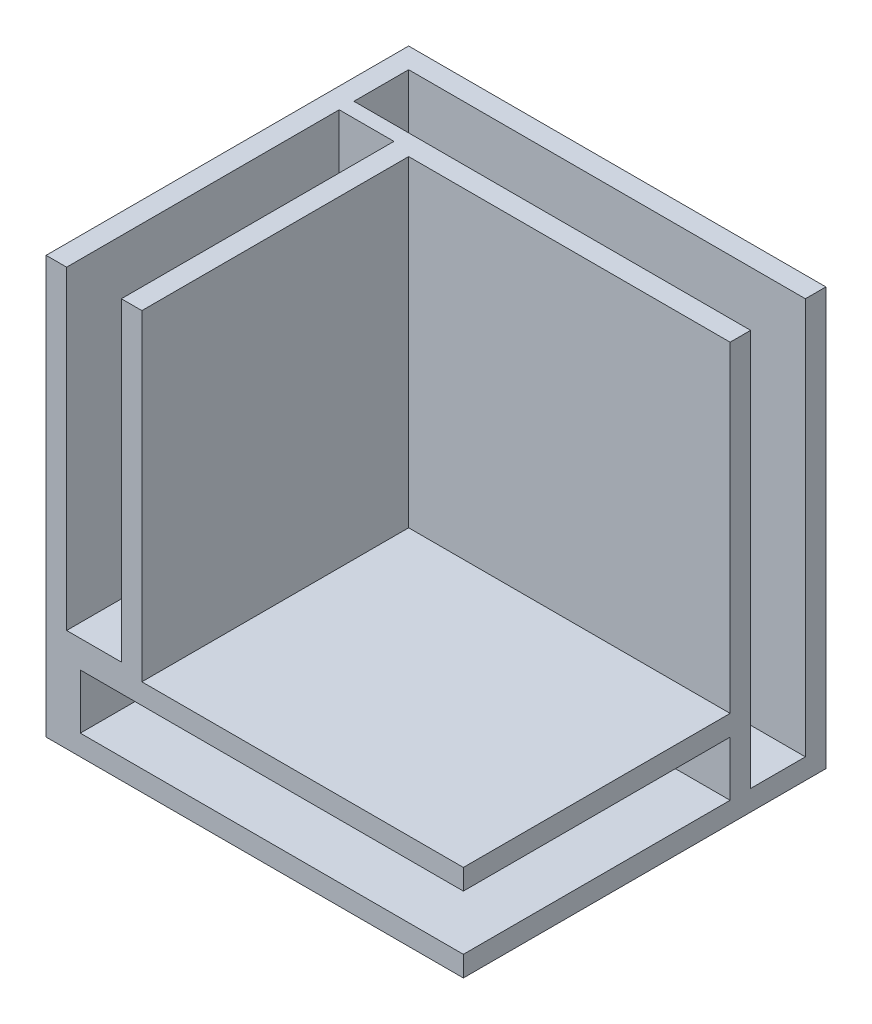
SolidWorks part; units mm, degrees
ref_plane "Front Plane" through (0, 0, 0) normal (0, 0, 1) x (1, 0, 0)
ref_plane "Top Plane" through (0, 0, 0) normal (0, 1, 0) x (1, 0, 0)
ref_plane "Right Plane" through (0, 0, 0) normal (1, 0, 0) x (0, 0, -1)
sketch "Sketch1" plane through (0, 0, 0) normal (0, 0, 1) x (1, 0, 0)
  line L1 (0, 0) -> (30, 0)
  line L2 (0, 0) -> (0, 30)
  line L3 (0, 30) -> (30, 30)
  line L4 (30, 0) -> (30, 30)
  dimension "D1" = 30
  dimension "D2" = 30
extrude "Boss-Extrude1" add sketch "Sketch1" along normal blind 6
sketch "Sketch2" plane through (0, 0, 6) normal (0, 0, 1) x (1, 0, 0)
  line L0 (0, 0) -> (30, 0) construction
  line L5 (6, 6) -> (0, 6)
  line L6 (30, 0) -> (6, 0)
  line L7 (30, 0) -> (30, 6)
  line L8 (30, 6) -> (6, 6)
  line L9 (6, 0) -> (6, 6)
  line L10 (6, 6) -> (6, 30)
  line L11 (30, 30) -> (0, 30) construction
  line L12 (6, 30) -> (0, 30)
  line L13 (0, 30) -> (0, 6)
  line L15 (5, 6) -> (6, 6)
  line L16 (5, 6) -> (5, 5)
  line L17 (5, 5) -> (6, 5)
  line L18 (6, 6) -> (6, 5)
  line M7 (0, 30) -> (0, 0)
  line M10 (30, 30) -> (0, 30)
  dimension "D1" = 6
  dimension "D2" = 6
  dimension "D3" = 1
  dimension "D4" = 1
extrude "Boss-Extrude4" add sketch "Sketch2" along normal blind 20 contours L5 L10 M10 M7 region at (3, 18, 6)
sketch "Sketch3" plane through (0, 0, 6) normal (0, 0, 1) x (1, 0, 0)
  line L1 (30, 0) -> (6, 0)
  line L2 (30, 0) -> (30, 6)
  line L3 (30, 6) -> (6, 6)
  line L4 (6, 0) -> (6, 6)
sketch "Sketch4" plane through (0, 0, 6) normal (0, 0, 1) x (1, 0, 0)
  line L1 (6, 6) -> (4, 6)
  line L2 (6, 6) -> (6, 4)
  line L3 (6, 4) -> (4, 4)
  line L4 (4, 6) -> (4, 4)
  dimension "D1" = 2
  dimension "D2" = 2
extrude "Boss-Extrude6" add sketch "Sketch4" along normal blind 20
sketch "Sketch5" plane through (0, 0, 6) normal (0, 0, 1) x (1, 0, 0)
  line L1 (6, 6) -> (30, 6)
  line L2 (6, 6) -> (6, 0)
  line L3 (6, 0) -> (30, 0)
  line L4 (30, 6) -> (30, 0)
extrude "Boss-Extrude7" add sketch "Sketch5" along normal blind 20
sketch "Sketch6" plane through (0, 0, 0) normal (0, 0, -1) x (-1, 0, 0)
  line L4 (0, 0) -> (0, 30)
  line L5 (0, 30) -> (-30, 30)
  line L6 (-30, 30) -> (-30, 0)
  line L7 (-30, 0) -> (0, 0)
  line L8 (0, 0) -> (0, 30)
  line L9 (0, 30) -> (-30, 30)
  line L10 (-30, 30) -> (-30, 0)
  line L11 (-30, 0) -> (0, 0)
  dimension "D1" = 0
shell "Shell2" thickness 1 removed face at (12, 30, 10.6667) removed face at (30, 12, 10.6667)
sketch "Sketch7" plane through (0, 5, 0) normal (0, -1, 0) x (1, 0, 0)
  line L1 (30, 5) -> (7, 5)
  line L2 (30, 5) -> (30, 6)
  line L3 (30, 6) -> (7, 6)
  line L4 (7, 5) -> (7, 6)
  dimension "D1" = 23
  dimension "D2" = 1
extrude "Boss-Extrude8" add sketch "Sketch7" along normal blind 5
sketch "Sketch8" plane through (0, 0, 6) normal (0, 0, 1) x (1, 0, 0)
  line L4 (6, 6) -> (30, 6)
  line L5 (30, 6) -> (30, 30)
  line L6 (30, 30) -> (6, 30)
  line L7 (6, 30) -> (6, 6)
  line L8 (6, 6) -> (30, 6)
  line L9 (30, 6) -> (30, 30)
  line L10 (30, 30) -> (6, 30)
  line L11 (6, 30) -> (6, 6)
  dimension "D1" = 0
sketch "Sketch9" plane through (5, 0, 0) normal (-1, 0, 0) x (0, 0, 1)
  line L1 (5, 30) -> (6.0751, 30)
  line L2 (5, 30) -> (5, 7)
  line L3 (5, 7) -> (6.0751, 7)
  line L4 (6.0751, 30) -> (6.0751, 7)
  dimension "D1" = 23
  dimension "D2" = 1.0751
extrude "Boss-Extrude9" add sketch "Sketch9" along normal blind 5
sketch "Sketch10" plane through (0, 0, 26) normal (0, 0, 1) x (1, 0, 0)
  line L0 (0, 30) -> (0, 6) construction
  line L1 (1, 7) -> (5, 7)
  line L2 (1, 7) -> (1, 30)
  line L3 (1, 30) -> (5, 30)
  line L4 (5, 7) -> (5, 30)
  line L6 (4, 6) -> (0, 6) construction
  dimension "D1" = 1
  dimension "D2" = 1
extrude "Cut-Extrude1" cut sketch "Sketch10" against normal blind 10
sketch "Sketch11" plane through (0, 0, 26) normal (0, 0, 1) x (1, 0, 0)
  line L0 (30, 0) -> (30, 6) construction
  line L1 (7, 5) -> (30, 5)
  line L2 (7, 5) -> (7, 1)
  line L3 (7, 1) -> (30, 1)
  line L4 (30, 5) -> (30, 1)
  line L5 (30, 6) -> (6, 6) construction
  line L6 (30, 0) -> (6, 0) construction
  line L7 (6, 0) -> (6, 6) construction
  point P12 (6, 3)
  dimension "D1" = 1
  dimension "D2" = 1
  dimension "D3" = 1
extrude "Cut-Extrude2" cut sketch "Sketch11" against normal blind 10
sketch "Sketch12" plane through (0, 0, 6) normal (0, 0, 1) x (1, 0, 0)
  line L6 (6, 0) -> (6, 4)
  line L7 (6, 4) -> (4, 4)
  line L8 (4, 4) -> (4, 6)
  line L9 (4, 6) -> (0, 6)
  line L10 (0, 6) -> (0, 0)
  line L11 (0, 0) -> (6, 0)
  line L12 (6, 0) -> (6, 4)
  line L13 (6, 4) -> (4, 4)
  line L14 (4, 4) -> (4, 6)
  line L15 (4, 6) -> (0, 6)
  line L16 (0, 6) -> (0, 0)
  line L17 (0, 0) -> (6, 0)
  dimension "D1" = 0
extrude "Boss-Extrude10" add sketch "Sketch12" along normal blind 20
sketch "Sketch13" plane through (7, 0, 0) normal (1, 0, 0) x (0, 0, -1)
  line L4 (-26, 1) -> (-6, 1)
  line L5 (-6, 1) -> (-6, 5)
  line L6 (-6, 5) -> (-26, 5)
  line L7 (-26, 5) -> (-26, 1)
  line L8 (-26, 1) -> (-6, 1)
  line L9 (-6, 1) -> (-6, 5)
  line L10 (-6, 5) -> (-26, 5)
  line L11 (-26, 5) -> (-26, 1)
  dimension "D1" = 0
extrude "Cut-Extrude3" cut sketch "Sketch13" against normal blind 5
sketch "Sketch14" plane through (0, 0, 0) normal (0, -1, 0) x (1, 0, 0)
  line L4 (0, 0) -> (30, 0)
  line L5 (30, 0) -> (30, 26)
  line L6 (30, 26) -> (0, 26)
  line L7 (0, 26) -> (0, 0)
  line L8 (0, 0) -> (30, 0)
  line L9 (30, 0) -> (30, 26)
  line L10 (30, 26) -> (0, 26)
  line L11 (0, 26) -> (0, 0)
  dimension "D1" = 0
extrude "Boss-Extrude11" add sketch "Sketch14" along normal blind 0.5
sketch "Sketch15" plane through (0, 0, 0) normal (-1, 0, 0) x (0, 0, 1)
  line L4 (26, 30) -> (0, 30)
  line L5 (0, 30) -> (0, -0.5)
  line L6 (0, -0.5) -> (26, -0.5)
  line L7 (26, -0.5) -> (26, 30)
  line L8 (26, 30) -> (0, 30)
  line L9 (0, 30) -> (0, -0.5)
  line L10 (0, -0.5) -> (26, -0.5)
  line L11 (26, -0.5) -> (26, 30)
  dimension "D1" = 0
extrude "Boss-Extrude12" add sketch "Sketch15" along normal blind 0.5
sketch "Sketch16" plane through (6, 0, 0) normal (1, 0, 0) x (0, 0, -1)
  line L4 (-26, 6) -> (-6, 6)
  line L5 (-6, 6) -> (-6, 30)
  line L6 (-6, 30) -> (-26, 30)
  line L7 (-26, 30) -> (-26, 6)
  line L8 (-26, 6) -> (-6, 6)
  line L9 (-6, 6) -> (-6, 30)
  line L10 (-6, 30) -> (-26, 30)
  line L11 (-26, 30) -> (-26, 6)
  dimension "D1" = 0
extrude "Boss-Extrude13" add sketch "Sketch16" along normal blind 0.5
sketch "Sketch17" plane through (0, 6, 0) normal (0, 1, 0) x (1, 0, 0)
  line L4 (30, -6) -> (6.5, -6)
  line L5 (6.5, -6) -> (6.5, -26)
  line L6 (6.5, -26) -> (30, -26)
  line L7 (30, -26) -> (30, -6)
  line L8 (30, -6) -> (6.5, -6)
  line L9 (6.5, -6) -> (6.5, -26)
  line L10 (6.5, -26) -> (30, -26)
  line L11 (30, -26) -> (30, -6)
  dimension "D1" = 0
sketch "Sketch18" plane through (0, 0, 6) normal (0, 0, 1) x (1, 0, 0)
  line L4 (6.5, 30) -> (6.5, 6.5)
  line L5 (6.5, 6.5) -> (30, 6.5)
  line L6 (30, 6.5) -> (30, 30)
  line L7 (30, 30) -> (6.5, 30)
  line L8 (6.5, 30) -> (6.5, 6.5)
  line L9 (6.5, 6.5) -> (30, 6.5)
  line L10 (30, 6.5) -> (30, 30)
  line L11 (30, 30) -> (6.5, 30)
  dimension "D1" = 0
sketch "Sketch19" plane through (0, 0, 0) normal (0, 0, -1) x (-1, 0, 0)
  line L4 (-30, -0.5) -> (0.5, -0.5)
  line L5 (0.5, -0.5) -> (0.5, 30)
  line L6 (0.5, 30) -> (-30, 30)
  line L7 (-30, 30) -> (-30, -0.5)
  line L8 (-30, -0.5) -> (0.5, -0.5)
  line L9 (0.5, -0.5) -> (0.5, 30)
  line L10 (0.5, 30) -> (-30, 30)
  line L11 (-30, 30) -> (-30, -0.5)
  dimension "D1" = 0
extrude "Boss-Extrude14" add sketch "Sketch19" along normal blind 0.5
sketch "Sketch20" plane through (0, 0, 6) normal (0, 0, 1) x (1, 0, 0)
  line L4 (30, 30) -> (6.5, 30)
  line L5 (6.5, 30) -> (6.5, 6)
  line L6 (6.5, 6) -> (30, 6)
  line L7 (30, 6) -> (30, 30)
  line L8 (30, 30) -> (6.5, 30)
  line L9 (6.5, 30) -> (6.5, 6)
  line L10 (6.5, 6) -> (30, 6)
  line L11 (30, 6) -> (30, 30)
  dimension "D1" = 0
extrude "Boss-Extrude15" add sketch "Sketch20" along normal blind 0.5
sketch "Sketch21" plane through (0, 6, 0) normal (0, 1, 0) x (1, 0, 0)
  line L4 (30, -26) -> (30, -6.5)
  line L5 (30, -6.5) -> (6.5, -6.5)
  line L6 (6.5, -6.5) -> (6.5, -26)
  line L7 (6.5, -26) -> (30, -26)
  line L8 (30, -26) -> (30, -6.5)
  line L9 (30, -6.5) -> (6.5, -6.5)
  line L10 (6.5, -6.5) -> (6.5, -26)
  line L11 (6.5, -26) -> (30, -26)
  dimension "D1" = 0
extrude "Boss-Extrude16" add sketch "Sketch21" along normal blind 0.5
sketch "Sketch25" plane through (0, 0, 6) normal (0, 0, 1) x (1, 0, 0)
  line L4 (2, 1) -> (30, 1)
  line L5 (30, 1) -> (30, 5)
  line L6 (30, 5) -> (2, 5)
  line L7 (2, 5) -> (2, 1)
  line L8 (2, 1) -> (30, 1)
  line L9 (30, 1) -> (30, 5)
  line L10 (30, 5) -> (2, 5)
  line L11 (2, 5) -> (2, 1)
  dimension "D1" = 0
extrude "Boss-Extrude17" add sketch "Sketch25" along normal blind 0.5
